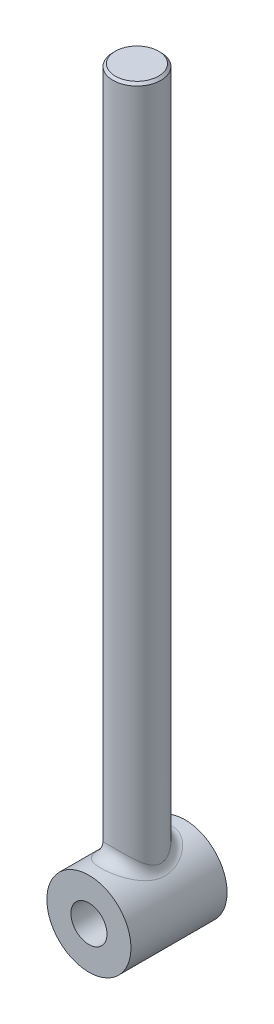
SolidWorks part; units mm, degrees
ref_plane "Front Plane" through (0, 0, 0) normal (0, 0, 1) x (1, 0, 0)
ref_plane "Top Plane" through (0, 0, 0) normal (0, 1, 0) x (1, 0, 0)
ref_plane "Right Plane" through (0, 0, 0) normal (1, 0, 0) x (0, 0, -1)
sketch "Sketch1" plane through (0, 0, 0) normal (0, 0, 1) x (1, 0, 0)
  circle A0 centre (0, 0) radius 11.25
  dimension "D1" = 22.5
extrude "Extrude-Thin1" add sketch "Sketch1" along normal mid plane 60 thin thin type one direction wall 15
sketch "Sketch2" plane through (0, 0, 0) normal (0, 1, 0) x (1, 0, 0)
  circle A0 centre (0, 0) radius 15
  dimension "D1" = 30
extrude "Boss-Extrude2" add sketch "Sketch2" along normal blind 450
fillet "Fillet1" radius 7.5 1 edges at (4.424, 25.8745, 14.3328)
sketch "Sketch3" plane through (0, 0, 30) normal (0, 0, 1) x (1, 0, 0)
  circle A0 centre (0, 0) radius 11.25 construction
  circle A1 centre (0, 0) radius 11.25
  dimension "D1" = 22.5
extrude "Cut-Extrude1" cut sketch "Sketch3" against normal blind 450
chamfer "Chamfer1" distance 1.5 angle 45 1 edges at (0, 450, 15)
